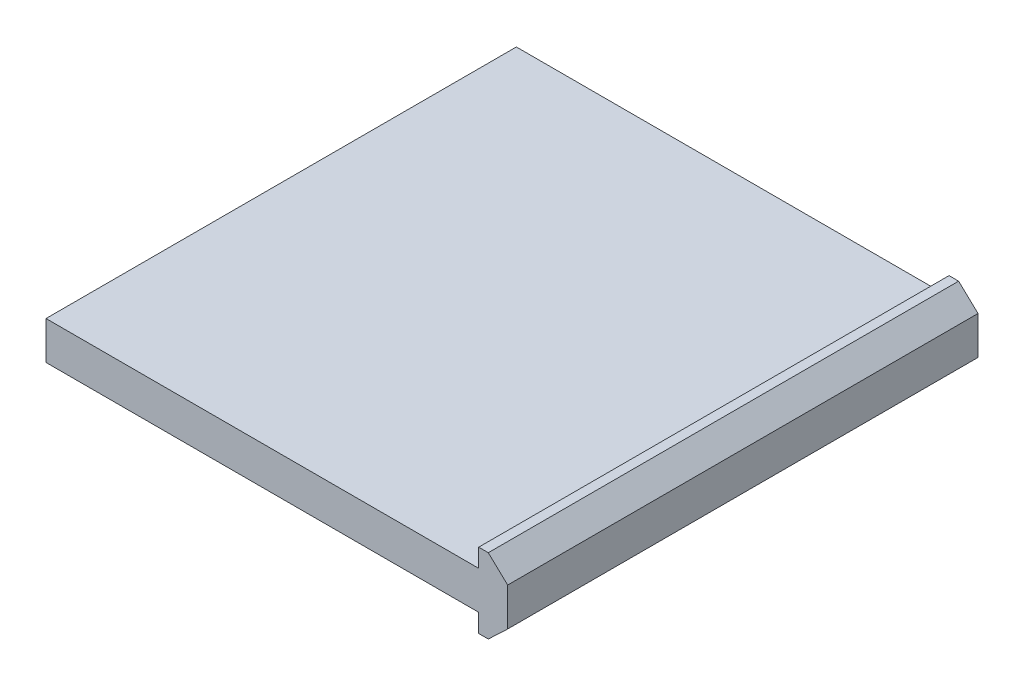
SolidWorks part; units mm, degrees
ref_plane "Front Plane" through (0, 0, 0) normal (0, 0, 1) x (1, 0, 0)
ref_plane "Top Plane" through (0, 0, 0) normal (0, 1, 0) x (1, 0, 0)
ref_plane "Right Plane" through (0, 0, 0) normal (1, 0, 0) x (0, 0, -1)
sketch "Sketch1" plane through (0, 0, 0) normal (0, 0, 1) x (1, 0, 0)
  line L0 (0, 4.05) -> (-92, 4.05)
  line L1 (0, -4.05) -> (-92, -4.05)
  line L2 (-92, -4.05) -> (-92, 4.05)
  line B0 (0, 7.95) -> (2.04, 7.95)
  line B1 (6.1524, 4.048) -> (6.1524, -4.048)
  line B2 (2.04, -7.95) -> (0, -7.95)
  line B3 (0, -7.95) -> (0, 7.95)
  line B4 (2.04, 7.95) -> (6.1524, 4.048)
  line B5 (6.1524, -4.048) -> (2.04, -7.95)
  line B6 (0, 4.05) -> (0, -4.05) construction
  dimension "D1" = 92
sketch_block_instance "Extrusion Profile-2"
sketch_block "Extrusion Profile" parameters "D1"=8.44, "D2"=2.6, "D3"=6, "D4"=16.7, "D6"=5.6686, "D7"=2.0404, "D8"=8.0963, "D9"=15.9, "D5"=2.4157
extrude "Boss-Extrude1" add sketch "Sketch1" along normal blind 100 contours L1 B3 L0 L2 | B2 B5 B1 B4 B0 B3 region at (-46, 0, 0) region at (2.7416, 0, 0)
